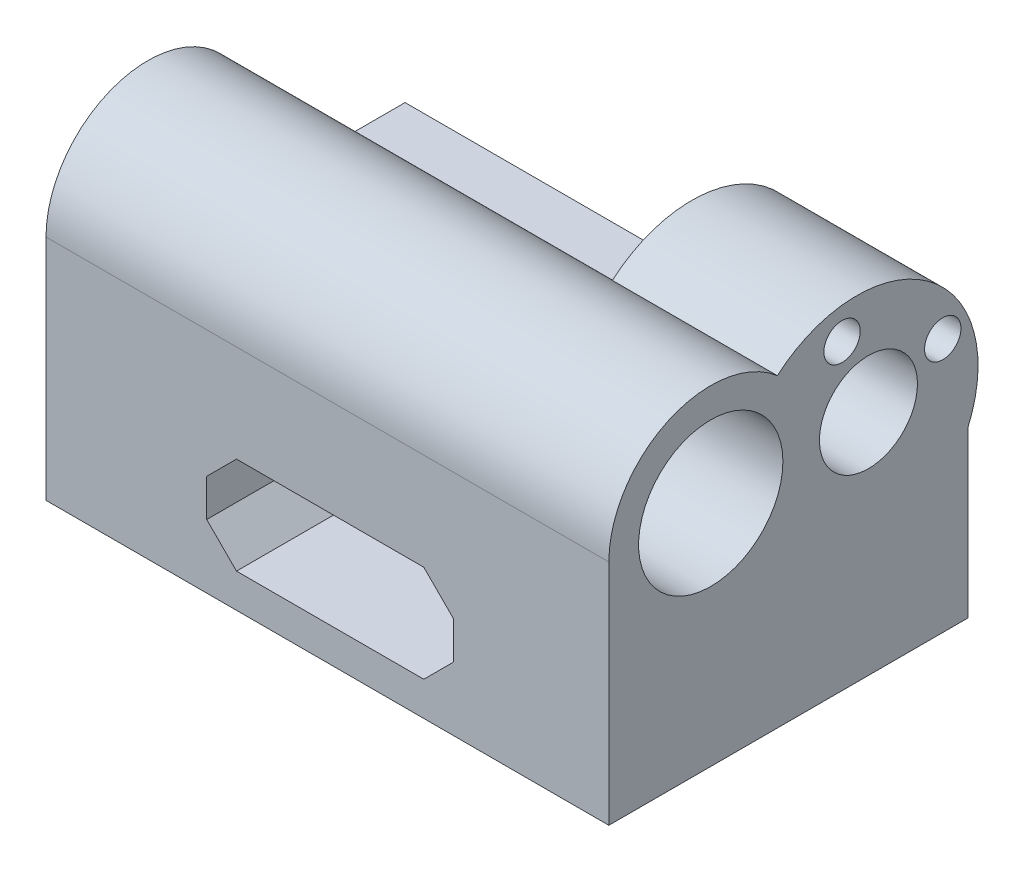
SolidWorks part; units mm, degrees
ref_plane "Front Plane" through (0, 0, 0) normal (0, 0, 1) x (1, 0, 0)
ref_plane "Top Plane" through (0, 0, 0) normal (0, 1, 0) x (1, 0, 0)
ref_plane "Right Plane" through (0, 0, 0) normal (1, 0, 0) x (0, 0, -1)
sketch "Sketch2" plane through (0, 0, 0) normal (0, 1, 0) x (1, 0, 0)
  line L1 (-29, -18.5) -> (29, -18.5)
  line L2 (-29, -18.5) -> (-29, 18.5)
  line L3 (-29, 18.5) -> (29, 18.5)
  line L4 (29, -18.5) -> (29, 18.5)
  line L5 (-29, -18.5) -> (29, 18.5) construction
  line L6 (-29, 18.5) -> (29, -18.5) construction
  point P0 (0, 0)
  dimension "D1" = 58
  dimension "D2" = 37
extrude "Boss-Extrude1" add sketch "Sketch2" along normal blind 17
sketch "Sketch3" plane through (29, 0, 0) normal (1, 0, 0) x (0, 0, -1)
  line L0 (-18.5, 0) -> (18.5, 0) construction
  line L1 (-18.5, 23.5) -> (-18.5, 17)
  line L2 (-18.5, 17) -> (-18.5, 0) construction
  line L5 (2.5, 23.5) -> (2.5, 17)
  line L6 (-18.5, 17) -> (18.5, 17) construction
  line L7 (-18.5, 17) -> (2.5, 17)
  arc A0 (2.5, 23.5) -> (-18.5, 23.5) centre (-8, 23.5) ccw
  dimension "D2" = 21
  dimension "D4" = 23.5
  dimension "D5" = 10.5
extrude "Boss-Extrude2" add sketch "Sketch3" against normal up to surface (58 mm away) up to face at (-29, 8.5, 0)
sketch "Sketch4" plane through (29, 0, 0) normal (1, 0, 0) x (0, 0, -1)
  line L1 (-18.5, 0) -> (18.5, 0) construction
  circle A0 centre (7.0436, 22) radius 12.5
  point P4 (8.8229, 23.5)
  dimension "D1" = 25
  dimension "D2" = 22
extrude "Boss-Extrude3" add sketch "Sketch4" against normal blind 17
sketch "Sketch5" plane through (0, 0, -18.5) normal (0, 0, -1) x (-1, 0, 0)
  line L0 (-13, 6.57) -> (-13, 10.427)
  line L1 (-13, 10.427) -> (-9.93, 13.497)
  line L2 (-9.93, 13.497) -> (9.37, 13.497)
  line L3 (9.37, 13.497) -> (12.44, 10.427)
  line L4 (12.44, 10.427) -> (12.44, 6.57)
  line L5 (12.44, 6.57) -> (9.37, 3.5)
  line L6 (9.37, 3.5) -> (-9.93, 3.5)
  line L7 (-9.93, 3.5) -> (-13, 6.57)
  line L8 (-29, 0) -> (29, 0) construction
  line L9 (-29, 17) -> (-29, 0) construction
  dimension "D1" = 3.857
  dimension "D2" = 3.857
  dimension "D3" = 135
  dimension "D4" = 135
  dimension "D5" = 3.07
  dimension "D6" = 3.07
  dimension "D7" = 3.07
  dimension "D8" = 3.07
  dimension "D9" = 19.3
  dimension "D10" = 3.5
  dimension "D11" = 16
extrude "Cut-Extrude1" cut sketch "Sketch5" against normal through all
sketch "Sketch6" plane through (0, 0, -18.5) normal (0, 0, -1) x (-1, 0, 0)
  line L0 (-29, 0) -> (29, 0) construction
  line L1 (-29, 17) -> (-29, 0) construction
  circle A0 centre (-23, 8.5) radius 4.076
  circle A1 centre (22, 8.5) radius 4.076
  dimension "D5" = 8.152
  dimension "D6" = 8.152
  dimension "D1" = 8.5
  dimension "D2" = 8.5
  dimension "D3" = 6
  dimension "D4" = 51
extrude "Cut-Extrude2" cut sketch "Sketch6" against normal blind 23
sketch "Sketch7" plane through (29, 0, 0) normal (1, 0, 0) x (0, 0, -1)
  line L0 (-18.5, 23.5) -> (-18.5, 0) construction
  line L1 (-18.5, 0) -> (18.5, 0) construction
  circle A0 centre (-8, 23.5) radius 7.4365
  circle A1 centre (8.2501, 23.5) radius 5.05
  point P4 (8.8229, 23.5512)
  point P6 (0, 0)
  dimension "D1" = 10.1
  dimension "D2" = 14.873
  dimension "D3" = 26.7501
  dimension "D4" = 23.5
extrude "Cut-Extrude3" cut sketch "Sketch7" against normal through all
sketch "Sketch8" plane through (29, 0, 0) normal (1, 0, 0) x (0, 0, -1)
  line L0 (8.2501, 23.5) -> (5.5314, 31.1566) construction
  line L3 (8.2501, 23.5) -> (15.9068, 26.2187) construction
  line L4 (5.5314, 31.1566) -> (6.1588, 29.3897) construction
  line L7 (15.9068, 26.2187) -> (14.1399, 25.5913) construction
  circle A1 centre (5.5314, 31.1566) radius 1.875
  circle A2 centre (15.9068, 26.2187) radius 1.875
  point P0 (15.3364, 24.2904)
  dimension "D1" = 3.75
  dimension "D2" = 6.25
  dimension "D3" = 3.75
  dimension "D7" = 6.25
extrude "Cut-Extrude4" cut sketch "Sketch8" against normal through all
sketch "Sketch9" plane through (12, 0, 0) normal (-1, 0, 0) x (0, 0, 1)
  circle A0 centre (-5.5314, 31.1566) radius 2.75
  circle A1 centre (-15.9068, 26.2187) radius 2.75
  point P6 (-15.3364, 24.2904)
  dimension "D1" = 5.5
  dimension "D2" = 5.5
